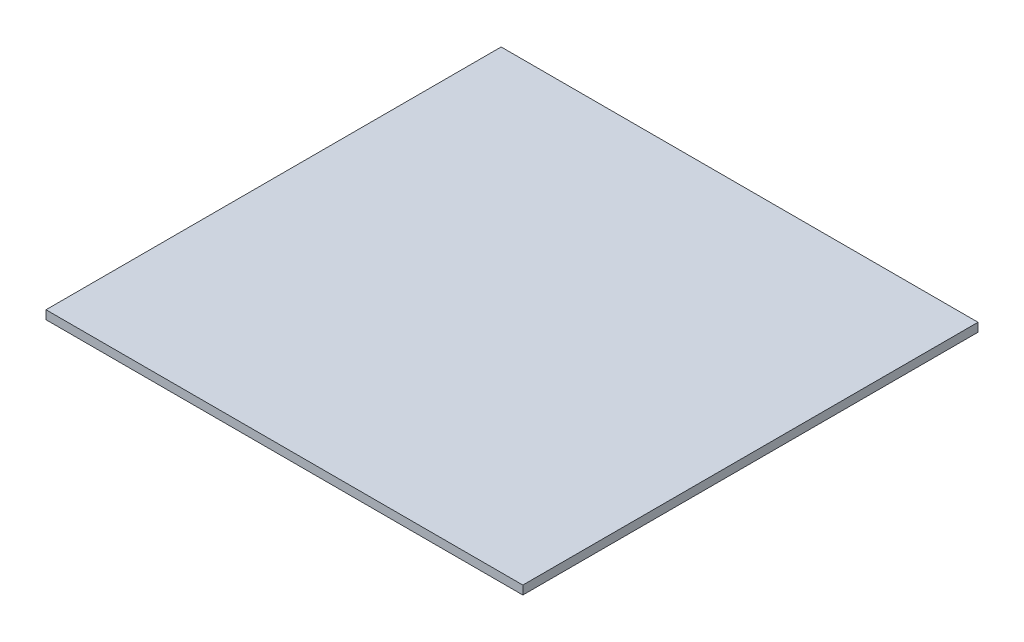
SolidWorks part; units mm, degrees
ref_plane "Спереди" through (0, 0, 0) normal (0, 0, 1) x (1, 0, 0)
ref_plane "Сверху" through (0, 0, 0) normal (0, 1, 0) x (1, 0, 0)
ref_plane "Справа" through (0, 0, 0) normal (1, 0, 0) x (0, 0, -1)
sketch "Эскиз1" plane through (0, 0, 0) normal (0, 1, 0) x (1, 0, 0)
  line L1 (-58.4225, 39.8335) -> (1041.5775, 39.8335)
  line L2 (-58.4225, 39.8335) -> (-58.4225, -1010.1665)
  line L3 (-58.4225, -1010.1665) -> (1041.5775, -1010.1665)
  line L4 (1041.5775, 39.8335) -> (1041.5775, -1010.1665)
  dimension "D1" = 1100
  dimension "D2" = 1050
sheet metal parameters "Листовой металл1" thickness 20 parameters "D1"=1.1, "Толщина"=20
base flange "Базовая кромка1" sketch "Эскиз1" thickness 20 reverse thickness direction no parameters "D1"=1.1
flat pattern "Развертка1" [suppressed]
sketch "Сгиб-Линии1" plane through (0, 0, 0) normal (0, 1, 0) x (1, 0, 0)
sketch3d "Граничная рамка1" [suppressed]
  line L0 (58.4225, 39.8335, 0) -> (58.4225, -1010.1665, 0) construction
  line L1 (-941.5775, 39.8335, 0) -> (-941.5775, -1010.1665, 0) construction
  line L2 (58.4225, 39.8335, 0) -> (-941.5775, 39.8335, 0) construction
  line L3 (58.4225, -1010.1665, 0) -> (-941.5775, -1010.1665, 0) construction
